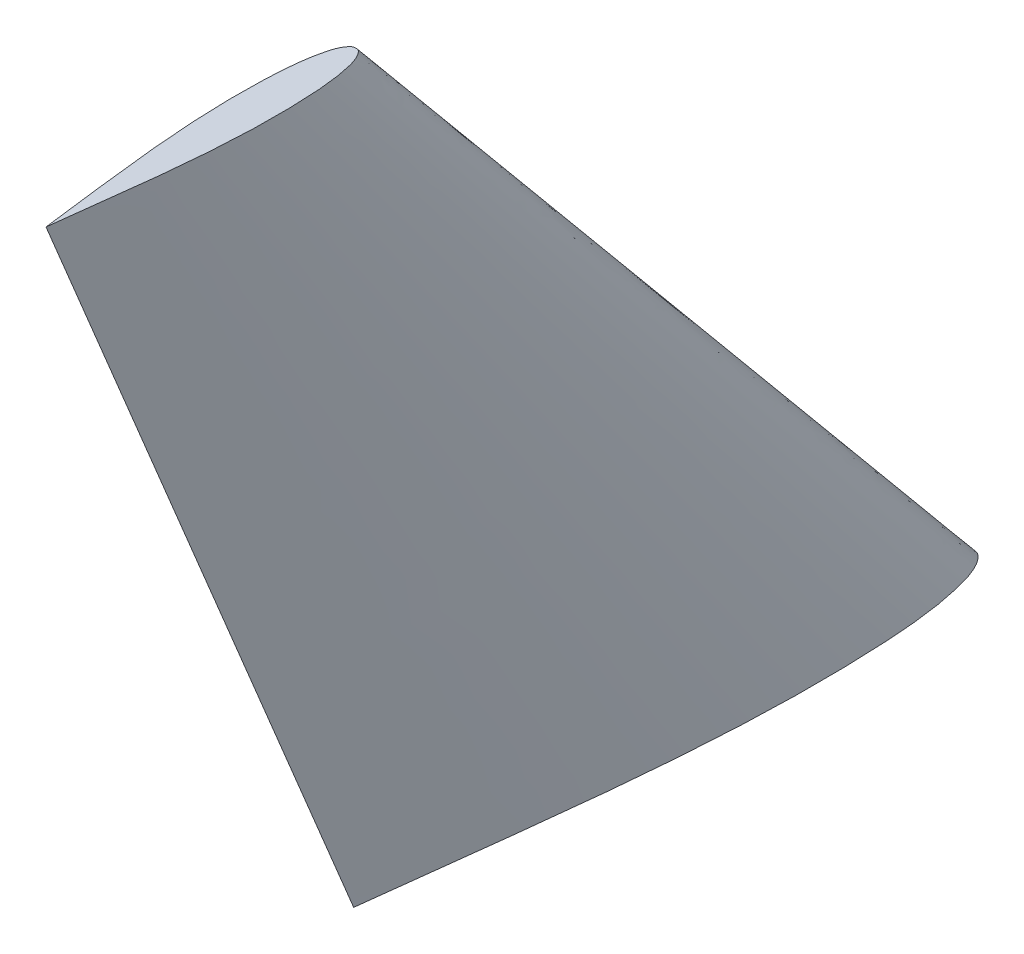
SolidWorks part; units mm, degrees
ref_plane "Front Plane" through (0, 0, 0) normal (0, 0, 1) x (1, 0, 0)
ref_plane "Top Plane" through (0, 0, 0) normal (0, 1, 0) x (1, 0, 0)
ref_plane "Right Plane" through (0, 0, 0) normal (1, 0, 0) x (0, 0, -1)
sketch "Sketch1" plane through (0, 0, 0) normal (0, 1, 0) x (1, 0, 0)
  line L0 (-215.8823, 1347.3324) -> (-486.544, 1347.3324) construction
  line L1 (0, -2790.1422) -> (0, 2790.1422) construction
  line L2 (-309.7777, -14582.8325) -> (-309.7777, -14310.2464) construction
  line L3 (423.7023, 3204.6344) -> (423.7023, 3740.6344) construction
  spline S0 degree 3 poles (0, 2790.1422) (32.4306, 2797.704) (84.2145, 2759.2657) (160.7843, 2647.8589) (216.2365, 2472.6267) (292.9453, 2117.6258) (431.0795, 352.4549) (168.4462, -1327.5077) (0, -2790.1422) knots 0 0 0 0 0.015892 0.031409 0.071418 0.111027 0.223281 1 1 1 1
  spline S1 degree 3 poles (0, 2790.1422) (-32.4306, 2797.704) (-84.2145, 2759.2657) (-160.7843, 2647.8589) (-216.2365, 2472.6267) (-292.9453, 2117.6258) (-431.0795, 352.4549) (-168.4462, -1327.5077) (0, -2790.1422) knots 0 0 0 0 0.015892 0.031409 0.071418 0.111027 0.223281 1 1 1 1
  point P6 (0, 0)
  dimension "D1" = 5580.2845
sketch "Sketch2" plane through (0, 0, 0) normal (1, 0, 0) x (0, 0, -1)
  line L0 (2790.1422, 0) -> (-2772.6535, 6696.456) construction
  line L1 (-2790.1422, 0) -> (2790.1422, 0) construction
  line L2 (-2790.1422, 0) -> (-5562.7952, 6696.456) construction
  line L3 (-5562.7952, 6696.456) -> (-2772.6535, 6696.456) construction
  line L4 (1395.0711, 0) -> (-3470.1889, 6696.456) construction
  line L5 (1553.9867, 1488.0757) -> (313.9209, 1488.0757) construction
  line L6 (313.9209, 1488.0757) -> (-3406.2767, 1488.0757) construction
  line L7 (313.9209, 1488.0757) -> (313.9209, 0) construction
  line L8 (1395.0711, 0) -> (1395.0711, 8848.7147) construction
  dimension "D1" = 1395.0711
  dimension "D2" = 5580.2845
  dimension "D3" = 2790.1416
  dimension "D4" = 697.5354
  dimension "D5" = 6696.456
  dimension "D6" = 1488.0757
  dimension "D7" = 36
ref_plane "Plane1" through (0, 6696.456, 0) normal (0, 1, 0) x (1, 0, 0)
sketch "Sketch3" plane through (0, 6696.456, 0) normal (0, 1, 0) x (1, 0, 0)
  line L0 (0, -2772.6535) -> (0, -5562.7952) construction
  line L1 (1.5245, -5940.7532) -> (-755.8625, -5716.5827) construction
  spline S0 degree 3 poles (0, -2772.6535) (16.9799, -2767.1453) (40.1911, -2785.806) (82.3452, -2843.2421) (112.4634, -2942.3407) (146.9755, -3121.7235) (216.027, -4000.0579) (88.1787, -4833.0101) (0, -5562.7952) knots 0 0 0 0 0.016437 0.028569 0.075697 0.12246 0.221964 1 1 1 1
  spline S1 degree 3 poles (0, -2772.6535) (-16.9799, -2767.1453) (-40.1911, -2785.806) (-82.3452, -2843.2421) (-112.4634, -2942.3407) (-146.9755, -3121.7235) (-216.027, -4000.0579) (-88.1787, -4833.0101) (0, -5562.7952) knots 0 0 0 0 0.016437 0.028569 0.075697 0.12246 0.221964 1 1 1 1
loft "Loft2" add profiles "Sketch1", "Sketch3" connector at (0, 0, 2790.1422) connector at (0, 6696.456, 5562.7952)
equation "\"D1@Sketch2\"=.25*\"D2@Sketch2\""
equation "\"D4@Sketch2\"=.25*\"D3@Sketch2\""
